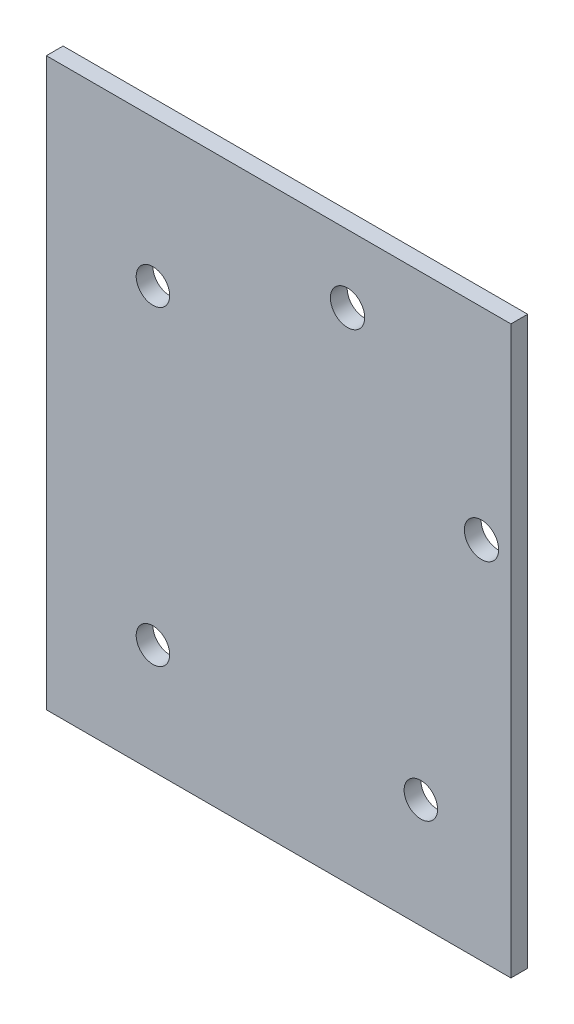
SolidWorks part; units mm, degrees
ref_plane "Front Plane" through (0, 0, 0) normal (0, 0, 1) x (1, 0, 0)
ref_plane "Top Plane" through (0, 0, 0) normal (0, 1, 0) x (1, 0, 0)
ref_plane "Right Plane" through (0, 0, 0) normal (1, 0, 0) x (0, 0, -1)
sketch "Sketch1" plane through (0, 0, 0) normal (0, 0, 1) x (1, 0, 0)
  line L1 (93.2809, 204.6053) -> (5.1872, 204.6053)
  line L2 (93.2809, 204.6053) -> (93.2809, 97.1939)
  line L3 (93.2809, 97.1939) -> (5.1872, 97.1939)
  line L4 (5.1872, 204.6053) -> (5.1872, 97.1939)
  line L5 (75.0021, 179.07) -> (49.6021, 179.07) construction
  line L6 (49.6021, 179.07) -> (49.6021, 128.27) construction
  line L9 (75.0021, 179.07) -> (75.0021, 128.27) construction
  circle A0 centre (25.4, 117.9286) radius 3.175
  circle A1 centre (25.4, 176.8929) radius 3.175
  circle A2 centre (76.2, 117.9286) radius 3.175
  circle A3 centre (87.7021, 166.37) radius 3.2512
  circle A4 centre (62.3021, 191.77) radius 3.2512
  point P17 (111.0615, 167.9575)
  dimension "D1" = 6.35
  dimension "D4" = 6.5024
  dimension "D2" = 20.7346
  dimension "D3" = 20.2128
  dimension "D6" = 12.7
  dimension "D7" = 12.7
  dimension "D8" = 12.7
  dimension "D9" = 5.5789
  dimension "D10" = 38.2353
  dimension "D5" = 12.7
extrude "Boss-Extrude1" add sketch "Sketch1" along normal blind 3.175
equation "\"80/20 to Center Hole\"= .64in"
equation "\"80/20 from Edge\"= 0.5in"
equation "\"D6@Sketch1\"=\"80/20 from Edge\""
equation "\"D8@Sketch1\"=\"80/20 from Edge\""
